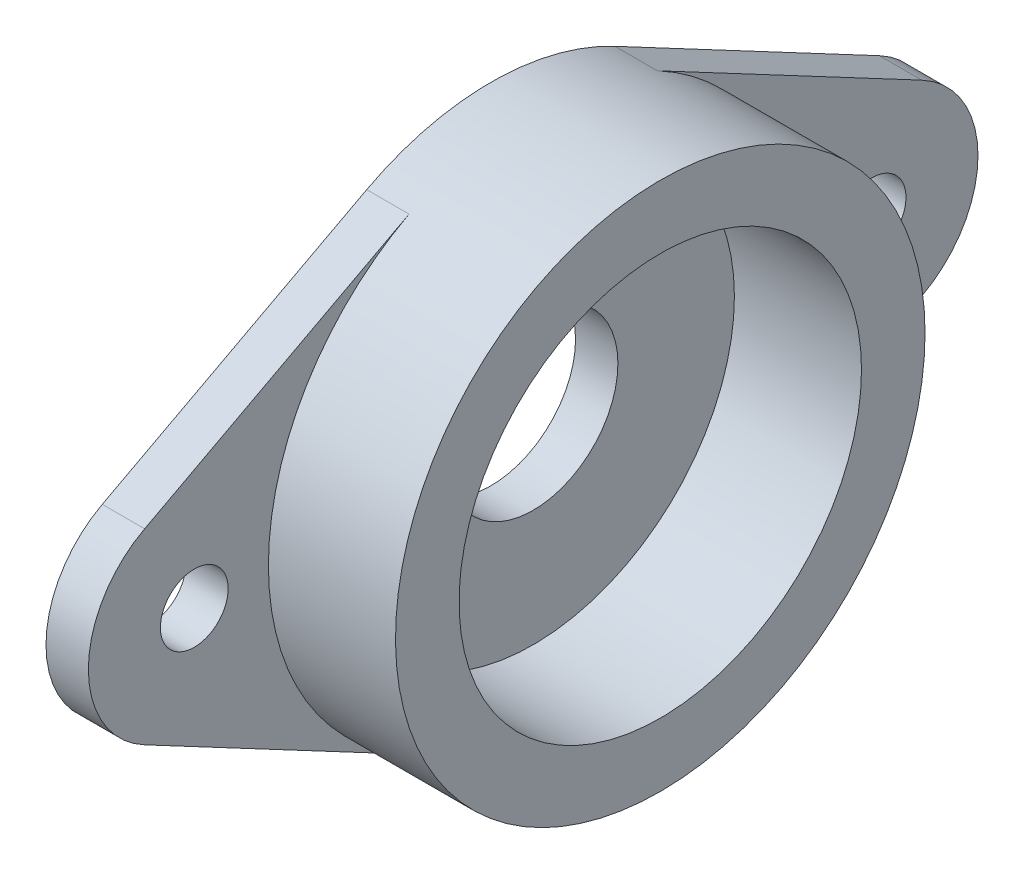
SolidWorks part; units mm, degrees
material "PLA (Orange)"
ref_plane "Front Plane" through (0, 0, 0) normal (0, 0, 1) x (1, 0, 0)
ref_plane "Top Plane" through (0, 0, 0) normal (0, 1, 0) x (1, 0, 0)
ref_plane "Right Plane" through (0, 0, 0) normal (1, 0, 0) x (0, 0, -1)
sketch "Sketch1" plane through (0, 0, 0) normal (1, 0, 0) x (0, 0, -1)
  line L0 (0, 0) -> (0, 7304.3141) construction
  line L1 (-18.3438, 4.4167) -> (-5.8594, 11.0416)
  line L2 (-18.3438, -4.4167) -> (-5.8594, -11.0416)
  line L3 (18.3438, -4.4167) -> (5.8594, -11.0416)
  line L4 (18.3438, 4.4167) -> (5.8594, 11.0416)
  circle A2 centre (0, 0) radius 9.5
  circle A3 centre (0, 0) radius 12.5
  arc A4 (-18.3438, -4.4167) -> (-18.3438, 4.4167) centre (-16, 0) cw
  circle A5 centre (-16, 0) radius 1.6
  circle A6 centre (16, 0) radius 1.6
  arc A7 (18.3438, -4.4167) -> (18.3438, 4.4167) centre (16, 0) ccw
  circle A8 centre (0, 0) radius 4
  dimension "D1" = 19
  dimension "D2" = 12.5
  dimension "D4" = 3.2
  dimension "D5" = 5
  dimension "D6" = 8
  dimension "D3" = 16
extrude "Boss-Extrude1" add sketch "Sketch1" along normal blind 2 contours A4 L2 A3 L1 A5 | L3 A7 L4 A3 A6 region at (0, 7.4926, 11.9761) region at (0, 7.4926, -11.9761)
extrude "Boss-Extrude2" add sketch "Sketch1<5>" along normal offset from surface (8 mm away) 6 contours L0 A3 A2 | A3 L0 A2 region at (0, 11.7868, -2.9337) up to face at (2, 0, 14.4) offset beyond the face yes
sketch "Sketch1<5>" plane through (0, 0, 0) normal (1, 0, 0) x (0, 0, -1) same geometry as "Sketch1"
extrude "Boss-Extrude3" add sketch "Sketch1<6>" along normal blind 2 contours L0 A2 A8 | A2 L0 A8 region at (0, 6.5275, -6.5275)
sketch "Sketch1<6>" plane through (0, 0, 0) normal (1, 0, 0) x (0, 0, -1) same geometry as "Sketch1"
